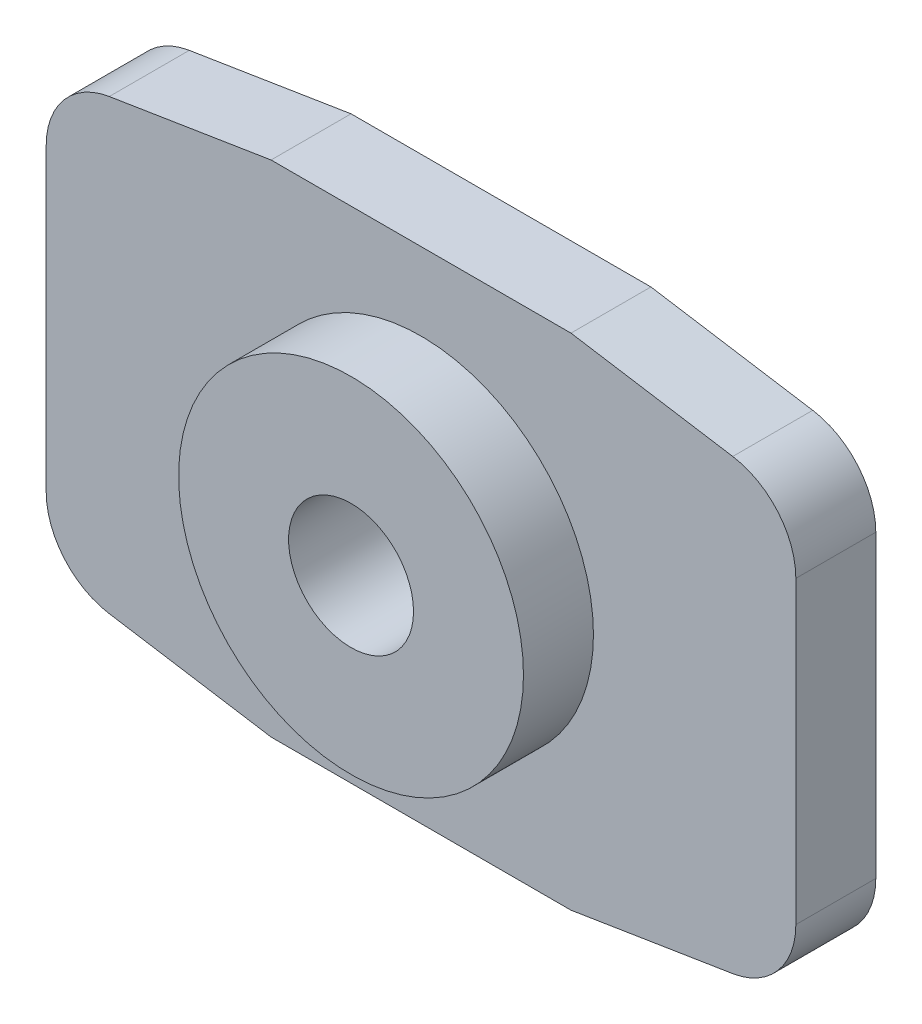
SolidWorks part; units mm, degrees
material "Plain Carbon Steel"
ref_plane "Front Plane" through (0, 0, 0) normal (0, 0, 1) x (1, 0, 0)
ref_plane "Top Plane" through (0, 0, 0) normal (0, 1, 0) x (1, 0, 0)
ref_plane "Right Plane" through (0, 0, 0) normal (1, 0, 0) x (0, 0, -1)
sketch "Sketch1" plane through (0, 0, 0) normal (0, 0, 1) x (1, 0, 0)
  line L0 (-7.5, 0) -> (7.5, 0) construction
  line L1 (-6.2374, 4.4811) -> (-3, 5)
  line L2 (-7.5, -3) -> (-7.5, 3)
  line L3 (-3, 5) -> (3, 5)
  line L4 (7.5, -3) -> (7.5, 3)
  line L5 (0, 5) -> (0, 0) construction
  line L6 (6.2374, 4.4811) -> (3, 5)
  line L7 (6.2374, -4.4811) -> (3, -5)
  line L8 (-3, -5) -> (3, -5)
  line L9 (-6.2374, -4.4811) -> (-3, -5)
  arc A0 (7.5, 3) -> (6.2374, 4.4811) centre (6, 3) ccw
  arc A1 (-7.5, -3) -> (-6.2374, -4.4811) centre (-6, -3) ccw
  arc A2 (7.5, -3) -> (6.2374, -4.4811) centre (6, -3) cw
  arc A3 (-7.5, 3) -> (-6.2374, 4.4811) centre (-6, 3) cw
  dimension "D3" = 6
  dimension "D5" = 1.5
  dimension "D1" = 15
  dimension "D2" = 10
  dimension "D4" = 6
extrude "Boss-Extrude1" add sketch "Sketch1" along normal blind 1.6
sketch "Sketch2" plane through (0, 0, 1.6) normal (0, 0, 1) x (1, 0, 0)
  line L0 (-7.5, 0) -> (0, 0) construction
  line L1 (-7.5, 3) -> (-7.5, -3) construction
  line L2 (0, 0) -> (0, 5) construction
  line L4 (3, 5) -> (-3, 5) construction
  circle A0 centre (0, 0) radius 3.45
  dimension "D2" = 6.9
extrude "Boss-Extrude2" add sketch "Sketch2" along normal blind 1.4
hole_wizard "M3x0.5 Tapped Hole1" positions "Sketch4" profile "Sketch3" tap size "M3x0.5" standard "ANSI Metric" end condition through all
sketch "Sketch4" plane through (0, 0, 3) normal (0, 0, 1) x (1, 0, 0)
  point P0 (0, 0)
sketch "Sketch3" plane through (0, 0, 3) normal (1, 0, 0) x (0, -1, 0)
  line L0 (0, 0) -> (0, 3)
  line L1 (0, 3) -> (1.25, 3)
  line L2 (1.25, 3) -> (1.25, 0)
  line L5 (1.25, 0) -> (0, 0)
  line L11 (0, -6.35) -> (0, 107.95) construction
  dimension "Thread Major Dia." = 2.5
  dimension "Thru Tap Drill Depth" = 3
